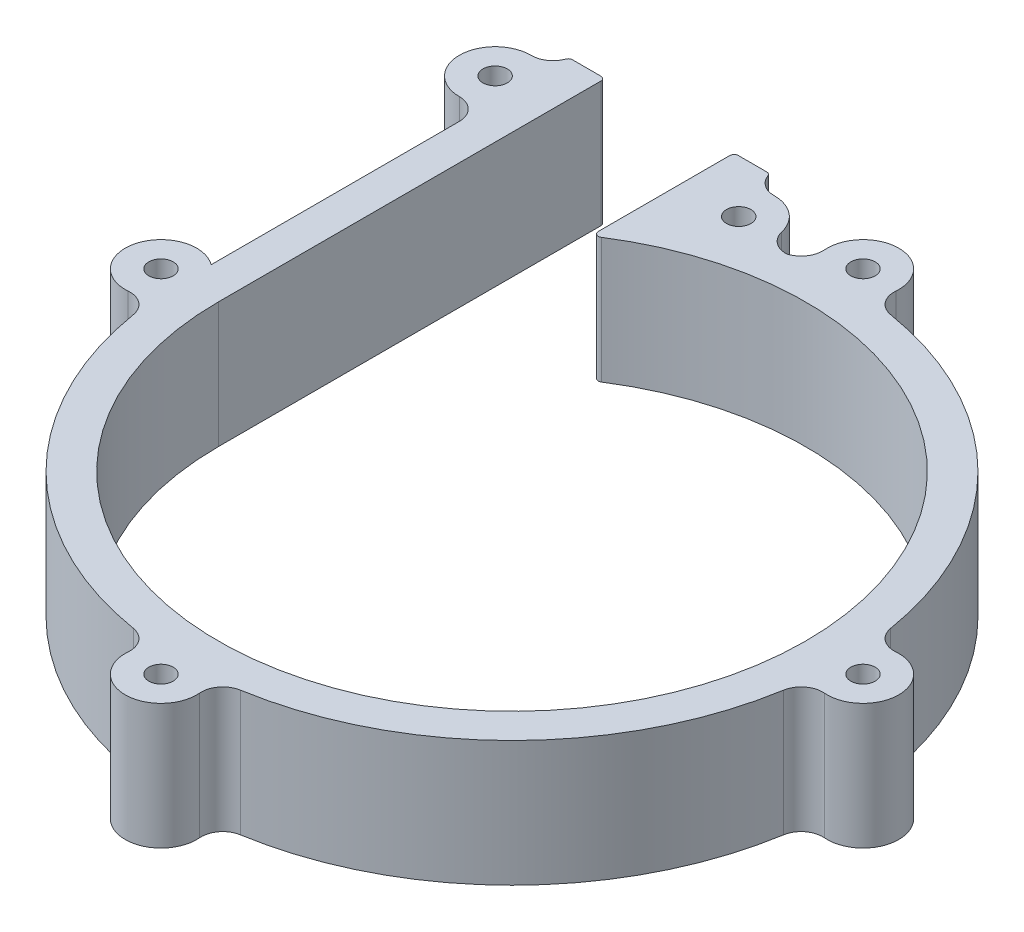
SolidWorks part; units mm, degrees
material "6061 合金"
ref_plane "前视基准面" through (0, 0, 0) normal (0, 0, 1) x (1, 0, 0)
ref_plane "上视基准面" through (0, 0, 0) normal (0, 1, 0) x (1, 0, 0)
ref_plane "右视基准面" through (0, 0, 0) normal (1, 0, 0) x (0, 0, -1)
sketch "草图1" plane through (0, 0, 0) normal (0, 1, 0) x (1, 0, 0)
  line L0 (-32, 0) -> (-32, 54) construction
  line L1 (-41, 0) -> (-41, 54)
  line L2 (-23, 54) -> (-23, 33.9411)
  line L3 (-41, 54) -> (-46, 54)
  line L4 (-46, 54) -> (-46, 50.6476)
  line L5 (-49, 0) -> (-49, 54) construction
  line L6 (-23, 54) -> (-18, 54)
  line L8 (-18, 54) -> (-18, 50.6476)
  line L10 (-49, 46.6476) -> (-15, 46.6476) construction
  line L11 (-46, 42.6476) -> (-46, 4)
  arc A0 (-41, 0) -> (-23, 33.9411) centre (0, 0) ccw
  circle A1 centre (0, 0) radius 49 construction
  circle A2 centre (0, 0) radius 32 construction
  circle A4 centre (0, 0) radius 41 construction
  circle A5 centre (0, 49) radius 1.7
  circle A6 centre (49, 0) radius 1.7
  circle A7 centre (0, -49) radius 1.7
  circle A8 centre (-49, 0) radius 1.7
  arc A35 (3.8722, 45.8367) -> (-3.8722, 45.8367) centre (0, 49) ccw
  arc A36 (-45.8367, -3.8722) -> (-3.8722, -45.8367) centre (0, 0) ccw
  arc A37 (45.8367, -3.8722) -> (45.8367, 3.8722) centre (49, 0) ccw
  arc A38 (-3.8722, -45.8367) -> (3.8722, -45.8367) centre (0, -49) ccw
  arc A39 (-46, 4) -> (-45.8367, -3.8722) centre (-49, 0) ccw
  arc A40 (-3.8722, 45.8367) -> (-10.3454, 44.8216) centre (0, 0) ccw
  arc A41 (45.8367, 3.8722) -> (3.8722, 45.8367) centre (0, 0) ccw
  arc A42 (3.8722, -45.8367) -> (45.8367, -3.8722) centre (0, 0) ccw
  circle A45 centre (-15, 46.6476) radius 1.7
  circle A47 centre (-49, 46.6476) radius 1.7
  arc A48 (-46, 50.6476) -> (-46, 42.6476) centre (-49, 46.6476) ccw
  arc A50 (-10.3454, 44.8216) -> (-18, 50.6476) centre (-15, 46.6476) ccw
  dimension "D1" = 82
  dimension "D3" = 9
  dimension "D6" = 3.4
  dimension "D8" = 8
  dimension "D12" = 8
  dimension "D4" = 54
  dimension "D9" = 10
  dimension "D2" = 5
  dimension "D5" = 9
  dimension "D10" = 5
  dimension "D11" = 5
  dimension "D7" = 4
extrude "凸台-拉伸1" add sketch "草图1" along normal blind 17.5
fillet "圆角1" radius 3 11 edges at (-3.8722, 8.75, -45.8367) (3.8722, 8.75, -45.8367) (45.8367, 8.75, -3.8722) (45.8367, 8.75, 3.8722) (3.8722, 8.75, 45.8367) (-3.8722, 8.75, 45.8367) (-45.8367, 8.75, 3.8722) (-46, 8.75, -42.6476) (-46, 8.75, -50.6476) (-18, 8.75, -50.6476) (-10.3454, 8.75, -44.8216)
fillet "圆角2" radius 0.6 5 edges at (-23, 8.75, -33.9411) (-41, 8.75, -54) (-23, 8.75, -54) (-46, 8.75, -54) (-18, 8.75, -54)
